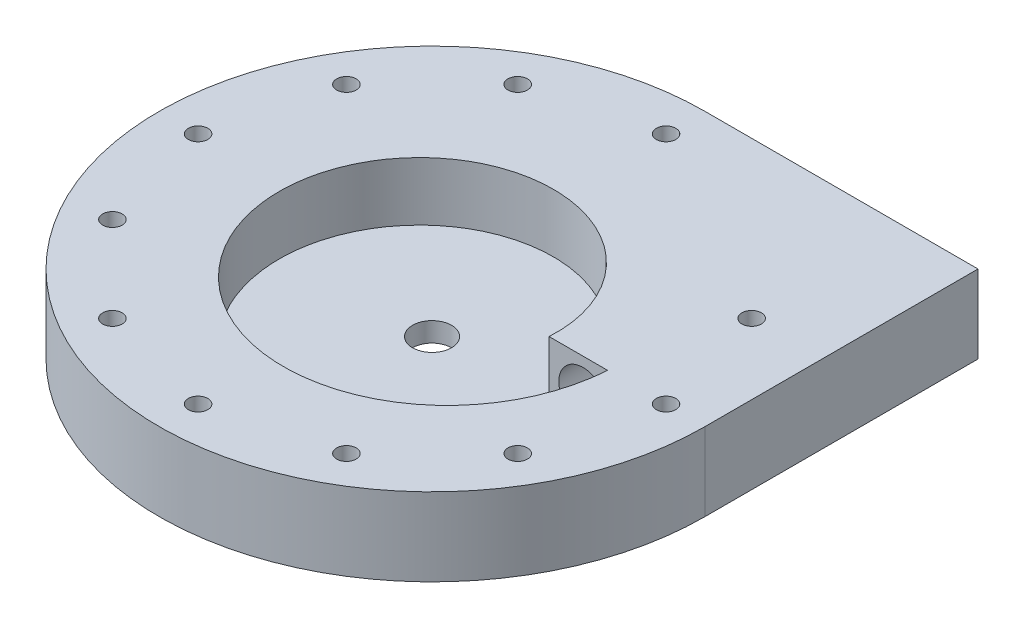
SolidWorks part; units mm, degrees
material "AISI 316 Annealed Stainless Steel Bar (SS)"
ref_plane "Front Plane" through (0, 0, 0) normal (0, 0, 1) x (1, 0, 0)
ref_plane "Top Plane" through (0, 0, 0) normal (0, 1, 0) x (1, 0, 0)
ref_plane "Right Plane" through (0, 0, 0) normal (1, 0, 0) x (0, 0, -1)
sketch "Sketch1" plane through (0, 0, 0) normal (0, 1, 0) x (1, 0, 0)
  line L0 (0, 0) -> (38.1, 0) construction
  line L1 (38.1, 0) -> (57.15, 0)
  line L2 (88.9, 0) -> (88.9, 88.9)
  line L3 (88.9, 88.9) -> (6.35, 88.9)
  line L4 (6.35, 88.9) -> (6.35, 88.6729)
  line L5 (47.625, 0) -> (47.625, 88.9) construction
  line L6 (6.35, 88.9) -> (0, 88.9)
  circle A0 centre (0, 0) radius 88.9
  circle A1 centre (0, 0) radius 6.35
  spline S0 degree 4 poles (29.5988, -21.5048) (29.8351, -21.22) (30.3001, -20.6441) (31.4238, -19.1734) (32.8568, -17.0118) (34.113, -14.7413) (35.1815, -12.3857) (35.8524, -10.6726) (36.3326, -9.2894) (36.7571, -7.8938) (37.0811, -6.6592) (37.3245, -5.5927) (37.5045, -4.6991) (37.6346, -3.9817) (37.751, -3.2617) (37.8534, -2.5399) (37.9255, -1.9518) (37.9744, -1.4973) (38.0054, -1.1831) (38.0222, -1.0035) (38.0424, -0.7748) (38.0658, -0.4876) (38.0909, -0.144) (38.1067, 0.0986) (38.1262, 0.4409) (38.1426, 0.7716) (38.158, 1.1548) (38.1712, 1.6096) (38.1802, 2.1518) (38.1802, 2.7648) (38.168, 3.5342) (38.1337, 4.4555) (38.065, 5.5299) (37.9473, 6.754) (37.7908, 7.9741) (37.5955, 9.1885) (37.3618, 10.3961) (37.0901, 11.5957) (36.7806, 12.7861) (36.2602, 14.5562) (35.4433, 16.878) (34.0888, 19.9822) (31.9638, 23.7352) (29.245, 27.4747) (25.8787, 31.0784) (22.0997, 34.2465) (18.4833, 36.5997) (14.6541, 38.5785) (11.22, 39.9409) (8.2776, 40.8467) (4.6752, 41.6527) (1.018, 42.1752) (-3.2917, 42.3676) (-8.2093, 42.0167) (-14.2651, 40.8758) (-21.2611, 38.4151) (-28.7662, 34.0526) (-35.122, 28.1428) (-39.5416, 22.1915) (-43.0486, 15.6831) (-45.6523, 8.5647) (-47.131, -0.1568) (-46.6549, -10.2288) (-44.0713, -19.9682) (-39.6379, -28.8272) (-33.5183, -36.6152) (-25.9784, -43.0353) (-17.3298, -47.8558) (-7.9143, -50.9141) (1.9103, -52.1192) (10.5502, -51.5343) (17.7692, -49.8909) (23.5588, -47.7937) (28.0161, -45.6963) (32.2624, -43.1995) (36.2636, -40.3263) (39.9882, -37.1026) (43.4074, -33.5568) (46.8815, -29.2396) (50.2256, -24.0643) (52.9395, -18.5267) (54.9867, -12.7154) (56.0714, -8.2271) (56.5719, -5.3479) (56.8158, -3.5193) (56.9065, -2.756) (56.9641, -2.2218) (57.0097, -1.76) (57.0445, -1.3812) (57.0705, -1.0803) (57.1017, -0.693) (57.1384, -0.1834) (57.1557, 0.0791) (57.18, 0.4966) (57.1965, 0.8062) (57.2081, 1.0431) (57.2182, 1.2727) (57.2273, 1.5007) (57.2418, 1.9027) (57.255, 2.3672) (57.2647, 2.8861) (57.2703, 3.5797) (57.2684, 4.2729) (57.2554, 5.0818) (57.2258, 6.0057) (57.1813, 6.9291) (57.122, 7.8517) (56.9554, 9.9251) (56.4457, 14.0562) (55.515, 18.3598) (54.112, 22.7722) (52.7365, 26.2052) (52.1806, 27.4758) (51.7925, 28.3148) (51.5941, 28.7323) knots 0 0 0 0 0 0.004243 0.008485 0.021213 0.029698 0.033941 0.03812 0.0423 0.04648 0.05066 0.052749 0.054839 0.056929 0.059019 0.061109 0.063199 0.063721 0.064244 0.064766 0.065289 0.066334 0.067379 0.06826 0.069141 0.070022 0.070903 0.072666 0.074428 0.07619 0.077953 0.081477 0.085002 0.088527 0.092051 0.095576 0.099101 0.102625 0.10615 0.109675 0.120249 0.130823 0.144922 0.15902 0.173119 0.187218 0.201317 0.208366 0.222465 0.229514 0.236563 0.250662 0.264761 0.27886 0.292959 0.321156 0.349353 0.377551 0.39165 0.405748 0.433946 0.464057 0.492254 0.520452 0.548649 0.576847 0.605044 0.633242 0.661439 0.689636 0.717834 0.731933 0.746031 0.76013 0.774229 0.788328 0.802426 0.816525 0.830624 0.851772 0.87292 0.887019 0.901118 0.904642 0.906405 0.908167 0.909929 0.91081 0.911692 0.912573 0.913454 0.915216 0.916541 0.917203 0.917866 0.918528 0.919191 0.919853 0.920515 0.923165 0.92449 0.925814 0.928464 0.931113 0.933763 0.936412 0.939062 0.941711 0.957608 0.984103 0.989402 0.994701 1 1 1 1 1 construction
  spline S1 degree 4 poles (38.1, 0) (38.1042, 0.065) (38.1122, 0.1956) (38.1262, 0.4409) (38.1426, 0.7716) (38.158, 1.1548) (38.1712, 1.6096) (38.1802, 2.1518) (38.1802, 2.7648) (38.168, 3.5342) (38.1337, 4.4555) (38.065, 5.5299) (37.9473, 6.754) (37.7908, 7.9741) (37.5955, 9.1885) (37.3618, 10.3961) (37.0901, 11.5957) (36.7806, 12.7861) (36.2602, 14.5562) (35.4433, 16.878) (34.0888, 19.9822) (31.9638, 23.7352) (29.245, 27.4747) (25.8787, 31.0784) (22.0997, 34.2465) (18.4833, 36.5997) (14.6541, 38.5785) (11.22, 39.9409) (8.2776, 40.8467) (4.6752, 41.6527) (1.018, 42.1752) (-3.2917, 42.3676) (-8.2093, 42.0167) (-14.2651, 40.8758) (-21.2611, 38.4151) (-28.7662, 34.0526) (-35.122, 28.1428) (-39.5416, 22.1915) (-43.0486, 15.6831) (-45.6523, 8.5647) (-47.131, -0.1568) (-46.6549, -10.2288) (-44.0713, -19.9682) (-39.6379, -28.8272) (-33.5183, -36.6152) (-25.9784, -43.0353) (-17.3298, -47.8558) (-7.9143, -50.9141) (1.9103, -52.1192) (10.5502, -51.5343) (17.7692, -49.8909) (23.5588, -47.7937) (28.0161, -45.6963) (32.2624, -43.1995) (36.2636, -40.3263) (39.9882, -37.1026) (43.4074, -33.5568) (46.8815, -29.2396) (50.2256, -24.0643) (52.9395, -18.5267) (54.9867, -12.7154) (56.0714, -8.2271) (56.5719, -5.3479) (56.8158, -3.5193) (56.9065, -2.756) (56.9641, -2.2218) (57.0097, -1.76) (57.0445, -1.3812) (57.0705, -1.0803) (57.1017, -0.693) (57.1284, -0.3226) (57.1416, -0.1301) (57.15, 0) knots 0.067379 0.067379 0.067379 0.067379 0.067379 0.06826 0.069141 0.070022 0.070903 0.072666 0.074428 0.07619 0.077953 0.081477 0.085002 0.088527 0.092051 0.095576 0.099101 0.102625 0.10615 0.109675 0.120249 0.130823 0.144922 0.15902 0.173119 0.187218 0.201317 0.208366 0.222465 0.229514 0.236563 0.250662 0.264761 0.27886 0.292959 0.321156 0.349353 0.377551 0.39165 0.405748 0.433946 0.464057 0.492254 0.520452 0.548649 0.576847 0.605044 0.633242 0.661439 0.689636 0.717834 0.731933 0.746031 0.76013 0.774229 0.788328 0.802426 0.816525 0.830624 0.851772 0.87292 0.887019 0.901118 0.904642 0.906405 0.908167 0.909929 0.91081 0.911692 0.912573 0.913454 0.915216 0.915216 0.915216 0.915216 0.915216
  dimension "D1" = 177.8
  dimension "D4" = 12.7
  dimension "D2" = 38.1
extrude "Boss-Extrude1" add sketch "Sketch1" against normal blind 25.4 contours L1 S1 | A0 S1 L1 | A0 L2 L3 L4 | A0 L4 L6 region at (47.625, 0, 1.4012) region at (69.0608, 0, -69.037) region at (-61.0838, 0, 61.0838) region at (4.7629, 0, -88.8319)
extrude "Cut-Extrude1" cut sketch "Sketch1<3>" against normal blind 19.05 contours L1 S1 region at (47.625, 0, 1.4012)
sketch "Sketch1<3>" plane through (0, 0, 0) normal (0, 1, 0) x (1, 0, 0) same geometry as "Sketch1"
sketch "Sketch2" plane through (0, 0, 0) normal (0, 0, 1) x (1, 0, 0)
  line L3 (38.1, -19.05) -> (57.15, -19.05) construction
  line L4 (57.15, -19.05) -> (57.15, 0) construction
  circle A0 centre (49.2125, -11.1125) radius 7.9375
  dimension "D1" = 15.875
extrude "Cut-Extrude3" cut sketch "Sketch2" against normal through all
hole_wizard "1/4 (0.25) Diameter Hole1" positions "3DSketch2" profile "Sketch3" hole size "1/4" standard "ANSI Inch"
sketch3d "3DSketch2"
  line L2 (76.2, 0, 0) -> (0, 0, 0) construction
  point P0 (76.2, 0, 0)
  dimension "D1" = 76.2
sketch "Sketch3" plane through (76.2, 0, 0) normal (1, 0, 0) x (0, 0, 1)
  line L0 (0, 0) -> (0, 78.1077)
  line L1 (0, 78.1077) -> (3.175, 76.2)
  line L2 (3.175, 76.2) -> (3.175, 0)
  line L5 (3.175, 0) -> (0, 0)
  line L10 (0, 78.1077) -> (-3.175, 76.2) construction
  line L11 (0, -6.35) -> (0, 107.95) construction
  dimension "Hole Dia." = 6.35
  dimension "Hole Depth" = 76.2
  dimension "Drill Angle" = 118
pattern_circular "CirPattern1" count 12 over 360 about axis through (0, -25.4, 0) along (0, 1, 0) skipping 2 of "1/4 (0.25) Diameter Hole1"
equation "\"Volute IR\" = 1.5"
equation "\"Volute OR\"= 1.5 + 3 / 4"
equation "\"D2@Sketch1\"=\"Volute IR\""
